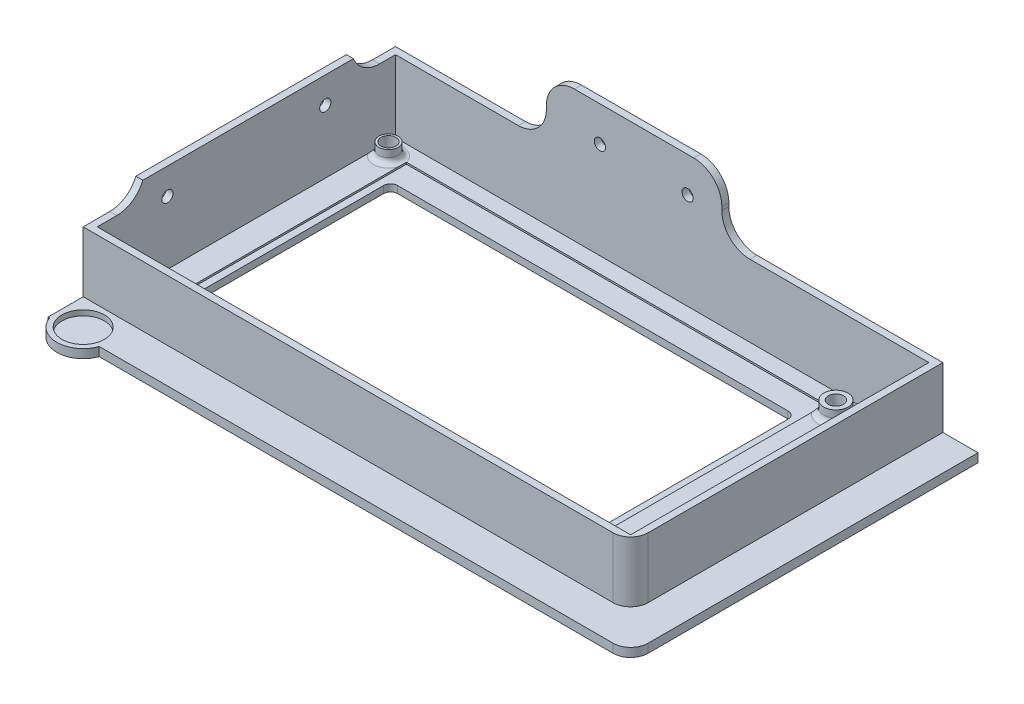
SolidWorks part; units mm, degrees
ref_plane "Alzado" through (0, 0, 0) normal (0, 0, 1) x (1, 0, 0)
ref_plane "Planta" through (0, 0, 0) normal (0, 1, 0) x (1, 0, 0)
ref_plane "Vista lateral" through (0, 0, 0) normal (1, 0, 0) x (0, 0, -1)
sketch "Croquis1" plane through (0, 0, 0) normal (0, 1, 0) x (1, 0, 0)
  line L1 (0, 0) -> (152, 0)
  line L2 (0, 0) -> (0, 85)
  line L3 (0, 85) -> (152, 85)
  line L4 (152, 0) -> (152, 85)
  dimension "D1" = 152
  dimension "D2" = 85
extrude "Saliente-Extruir1" add sketch "Croquis1" along normal blind 1.5
sketch "Croquis2" plane through (0, 1.5, 0) normal (0, 1, 0) x (1, 0, 0)
  line L0 (154, 87) -> (-2, 87)
  line L1 (-2, 87) -> (-2, -2)
  line L2 (-2, -2) -> (154, -2)
  line L3 (154, -2) -> (154, 87)
  line L4 (0, 85) -> (0, 0)
  line L5 (0, 0) -> (152, 0)
  line L6 (152, 0) -> (152, 85)
  line L7 (152, 85) -> (0, 85)
  line L8 (0, 85) -> (0, 0)
  line L9 (0, 0) -> (152, 0)
  line L10 (152, 0) -> (152, 85)
  line L11 (152, 85) -> (0, 85)
  dimension "D1" = 0
  dimension "D2" = 2
extrude "Saliente-Extruir3" add sketch "Croquis2" against normal up to surface (1.5 mm away) and the other way blind 5 up to face at (76, 0, -42.5)
sketch "Croquis3" plane through (0, 1.5, 0) normal (0, 1, 0) x (1, 0, 0)
  line L0 (0, 85) -> (0, 0) construction
  line L1 (152, 85) -> (0, 85) construction
  line L2 (76, 85) -> (76, 0) construction
  line L3 (0, 0) -> (152, 0) construction
  line L4 (0, 42.5) -> (152, 42.5) construction
  line L5 (0, 85) -> (0, 0) construction
  line L6 (152, 0) -> (152, 85) construction
  line L7 (0, 0) -> (152, 0) construction
  circle A0 centre (3.5, 79.5) radius 2.75
  circle A3 centre (3.5, 3.5) radius 3.45
  circle A4 centre (131, 79.5) radius 3.45
  circle A5 centre (131, 3.5) radius 3.45
  circle A6 centre (148.4, 3.5) radius 3.45
  circle A7 centre (148.4, 81.5) radius 3.45
  dimension "D1" = 5.5
  dimension "D4" = 6.9
  dimension "D2" = 3.5
  dimension "D3" = 5.5
  dimension "D5" = 127.5
  dimension "D6" = 5.5
  dimension "D7" = 3.5
  dimension "D8" = 3.5
  dimension "D9" = 3.5
  dimension "D10" = 127.5
  dimension "D11" = 3.6
extrude "Saliente-Extruir4" add sketch "Croquis3" along normal blind 3.5
sketch "Croquis4" plane through (0, 0, 0) normal (0, -1, 0) x (1, 0, 0)
  line L0 (-2, -87) -> (-2, 2) construction
  line L1 (7.6, -80.5) -> (127.1, -80.5)
  line L2 (7.6, -80.5) -> (7.6, -2)
  line L3 (7.6, -2) -> (127.1, -2)
  line L4 (127.1, -80.5) -> (127.1, -2)
  line L5 (154, -87) -> (-2, -87) construction
  dimension "D1" = 119.5
  dimension "D2" = 78.5
  dimension "D3" = 9.6
  dimension "D4" = 6.5
extrude "Cortar-Extruir1" cut sketch "Croquis4" against normal up to surface (1.5 mm away) up to face at (148.4, 1.5, -84.95)
sketch "Croquis5" plane through (0, 5, 0) normal (0, 1, 0) x (1, 0, 0)
  circle A0 centre (131, 3.5) radius 2.15
  circle A1 centre (3.5, 3.5) radius 2.15
  circle A2 centre (3.5, 79.5) radius 2.15
  circle A3 centre (131, 79.5) radius 2.15
  circle A4 centre (148.4, 3.5) radius 2.15
  circle A5 centre (148.4, 81.5) radius 2.15
  dimension "D1" = 4.3
extrude "Cortar-Extruir2" cut sketch "Croquis5" against normal blind 3
fillet "Redondeo1" radius 1.5 6 edges at (131, 1.5, -82.95) (3.5, 1.5, -82.25) (3.5, 1.5, -6.95) (131, 1.5, -6.95) (148.4, 1.5, -84.95) (148.4, 1.5, -6.95)
sketch "Croquis7" plane through (0, 6.5, 0) normal (0, 1, 0) x (1, 0, 0)
  line L0 (-2, -2) -> (154, -2) construction
  line L1 (0, 0) -> (152, 0) construction
  line L2 (0, 85) -> (0, 0) construction
  line L3 (-2, 87) -> (-2, -2) construction
  line L4 (152, 85) -> (0, 85) construction
  line L5 (154, 87) -> (-2, 87) construction
  line L6 (154, -2) -> (154, 87) construction
  line L7 (152, 0) -> (152, 85) construction
  line L8 (-2, -2) -> (86, -2)
  line L9 (0, 0) -> (86, 0)
  line L10 (0, 85) -> (0, 0)
  line L11 (-2, 87) -> (-2, -2)
  line L12 (152, 85) -> (0, 85)
  line L13 (154, 87) -> (-2, 87)
  line L14 (154, -2) -> (154, 87)
  line L15 (152, 0) -> (152, 85)
  line L16 (86, -2) -> (154, -2)
  line L21 (86, 0) -> (152, 0)
extrude "Saliente-Extruir5" add sketch "Croquis7" along normal blind 15.5
sketch "Croquis9" plane through (0, 22, 0) normal (0, 1, 0) x (1, 0, 0)
  line L1 (93, 85) -> (43, 85)
  line L2 (93, 85) -> (93, 87)
  line L3 (93, 87) -> (43, 87)
  line L4 (43, 85) -> (43, 87)
  line L5 (154, 87) -> (-2, 87) construction
  dimension "D1" = 50
  dimension "D2" = 45
  dimension "D3" = 59
extrude "Saliente-Extruir6" add sketch "Croquis9" along normal blind 17
sketch "Croquis10" plane through (0, 22, 0) normal (0, 1, 0) x (1, 0, 0)
  line L0 (0, 77.0891) -> (0, 7.0004) construction
  line L1 (0, 13) -> (-2, 13)
  line L2 (0, 13) -> (0, 73)
  line L3 (0, 73) -> (-2, 73)
  line L4 (-2, 13) -> (-2, 73)
  line L5 (-2, 87) -> (-2, -2) construction
  line L6 (-2, -2) -> (154, -2) construction
  dimension "D1" = 60
  dimension "D2" = 15
extrude "Saliente-Extruir7" add sketch "Croquis10" along normal blind 5
sketch "Croquis11" plane through (0, 0, 0) normal (1, 0, 0) x (0, 0, -1)
  line L0 (0, 22) -> (0, 1.5) construction
  line L1 (13, 27) -> (73, 27) construction
  circle A0 centre (20, 19.5) radius 1.6
  circle A1 centre (65, 19.5) radius 1.6
  dimension "D1" = 3.2
  dimension "D2" = 45
  dimension "D3" = 20
  dimension "D4" = 7.5
extrude "Cortar-Extruir4" cut sketch "Croquis11" against normal up to surface (2 mm away) up to face at (-2, 17.75, -42.75)
sketch "Croquis12" plane through (0, 0, -85) normal (0, 0, 1) x (1, 0, 0)
  line L0 (93, 39) -> (93, 22) construction
  line L2 (43, 39) -> (93, 39) construction
  circle A0 centre (83.25, 29) radius 1.6
  circle A1 centre (58.25, 29) radius 1.6
  dimension "D2" = 3.2
  dimension "D1" = 10
  dimension "D3" = 9.75
  dimension "D4" = 25
extrude "Cortar-Extruir5" cut sketch "Croquis12" against normal up to surface (2 mm away) up to face at (72, 20.75, -87)
fillet "Redondeo2" radius 8 6 edges at (-1, 22, -73) (-1, 22, -13) (93, 39, -86) (43, 39, -86) (43, 22, -86) (93, 22, -86)
sketch "Croquis13" plane through (0, 0, 2) normal (0, 0, 1) x (1, 0, 0)
  line L0 (-2, 22) -> (-2, 0) construction
  line L1 (-2, 4.75) -> (154, 4.75)
  line L2 (-2, 4.75) -> (-2, 2.25)
  line L3 (-2, 2.25) -> (154, 2.25)
  line L4 (154, 4.75) -> (154, 2.25)
  line L5 (154, 22) -> (154, 0) construction
  line L6 (-2, 0) -> (154, 0) construction
  dimension "D1" = 2.5
  dimension "D2" = 2.25
extrude "Saliente-Extruir8" add sketch "Croquis13" along normal blind 10
sketch "Croquis14" plane through (154, 0, 0) normal (1, 0, 0) x (0, 0, -1)
  line L0 (87, 22) -> (87, 0) construction
  line L1 (-12, 4.75) -> (87, 4.75)
  line L2 (-12, 4.75) -> (-12, 2.25)
  line L3 (-12, 2.25) -> (87, 2.25)
  line L4 (87, 4.75) -> (87, 2.25)
  line L5 (-12, 2.25) -> (-2, 2.25) construction
extrude "Saliente-Extruir9" add sketch "Croquis14" along normal blind 10
fillet "Redondeo3" radius 5 2 edges at (154, 1.125, 2) (164, 3.5, 12)
sketch "Croquis15" plane through (0, 4.75, 0) normal (0, 1, 0) x (1, 0, 0)
  line L4 (-2, -2) -> (149, -2) construction
  line L5 (-2, -12) -> (-2, -2) construction
  circle A0 centre (5.5, -9.5) radius 7.5
  dimension "D1" = 15
extrude "Saliente-Extruir10" add sketch "Croquis15" against normal up to surface (2.5 mm away) up to face at (117.7589, 2.25, -17.4911)
sketch "Croquis16" plane through (0, 4.75, 0) normal (0, 1, 0) x (1, 0, 0)
  arc A1 (-1.5711, -12) -> (12.5711, -12) centre (5.5, -9.5) ccw construction
  arc A3 (-1.5711, -12) -> (12.5711, -12) centre (5.5, -9.5) ccw construction
  circle A4 centre (5.5, -9.5) radius 6.05
  dimension "D1" = 12.1
extrude "Cortar-Extruir6" cut sketch "Croquis16" against normal blind 1.5
sketch "Croquis17" plane through (0, 0, 0) normal (0, -1, 0) x (1, 0, 0)
  line L0 (127.1, -2) -> (7.6, -2) construction
  line L1 (127.1, -80.5) -> (127.1, -2) construction
  line L2 (7.6, -2) -> (7.6, -80.5) construction
  line L3 (7.6, -80.5) -> (127.1, -80.5) construction
  line L4 (154, -87) -> (154, -3)
  line L5 (149, 2) -> (-2, 2)
  line L6 (-2, 2) -> (-2, -87)
  line L7 (-2, -87) -> (154, -87)
  line L8 (154, -87) -> (154, -3)
  line L9 (149, 2) -> (-2, 2)
  line L10 (-2, 2) -> (-2, -87)
  line L11 (-2, -87) -> (154, -87)
  line L12 (7.6, -80.5) -> (127.1, -80.5)
  line L13 (7.6, -2) -> (7.6, -80.5)
  line L14 (127.1, -80.5) -> (127.1, -2)
  line L15 (127.1, -2) -> (7.6, -2)
  arc A1 (154, -3) -> (149, 2) centre (149, -3) ccw
  arc A2 (154, -3) -> (149, 2) centre (149, -3) ccw
  dimension "D1" = 0
extrude "Saliente-Extruir11" add sketch "Croquis17" along normal blind 1
sketch "Croquis18" plane through (0, -1, 0) normal (0, -1, 0) x (1, 0, 0)
  line L0 (127.1, -80.5) -> (127.1, -2) construction
  line L1 (7.6, -2) -> (127.1, -2)
  line L2 (7.6, -2) -> (7.6, -6.85)
  line L3 (7.6, -6.85) -> (127.1, -6.85)
  line L4 (127.1, -2) -> (127.1, -6.85)
  line L5 (7.6, -80.5) -> (127.1, -80.5)
  line L6 (7.6, -80.5) -> (7.6, -74)
  line L7 (7.6, -74) -> (127.1, -74)
  line L8 (127.1, -80.5) -> (127.1, -74)
  line L10 (127.1, -2) -> (124.9, -2)
  line L11 (127.1, -2) -> (127.1, -80.5)
  line L12 (127.1, -80.5) -> (124.9, -80.5)
  line L13 (124.9, -2) -> (124.9, -80.5)
  line L14 (7.6, -6.85) -> (9.6, -6.85)
  line L15 (7.6, -6.85) -> (7.6, -74)
  line L16 (7.6, -74) -> (9.6, -74)
  line L17 (9.6, -6.85) -> (9.6, -74)
  line M14 (7.6, -80.5) -> (7.6, -2)
  line M15 (7.6, -2) -> (127.1, -2)
  line M16 (127.1, -2) -> (127.1, -80.5)
  line M17 (127.1, -80.5) -> (7.6, -80.5)
  dimension "D1" = 4.85
  dimension "D2" = 6.5
  dimension "D3" = 2.2
  dimension "D4" = 2
extrude "Saliente-Extruir12" add sketch "Croquis18" against normal blind 2 contours L13 L3 M15 M14 | L17 L3 L7 M14 | L13 L7 L5 M14 | L3 L13 L7 M16 | L1 L13 L3 M16 | L7 L13 M17 M16 region at (66.25, -1, -4.425) region at (126, -1, -4.425) region at (8.6, -1, -40.425) region at (126, -1, -40.425) region at (66.25, -1, -77.25) region at (126, -1, -77.25)
fillet "Redondeo4" radius 2 4 edges at (9.6, 0, -74) (124.9, 0, -74) (124.9, 0, -6.85) (9.6, 0, -6.85)
